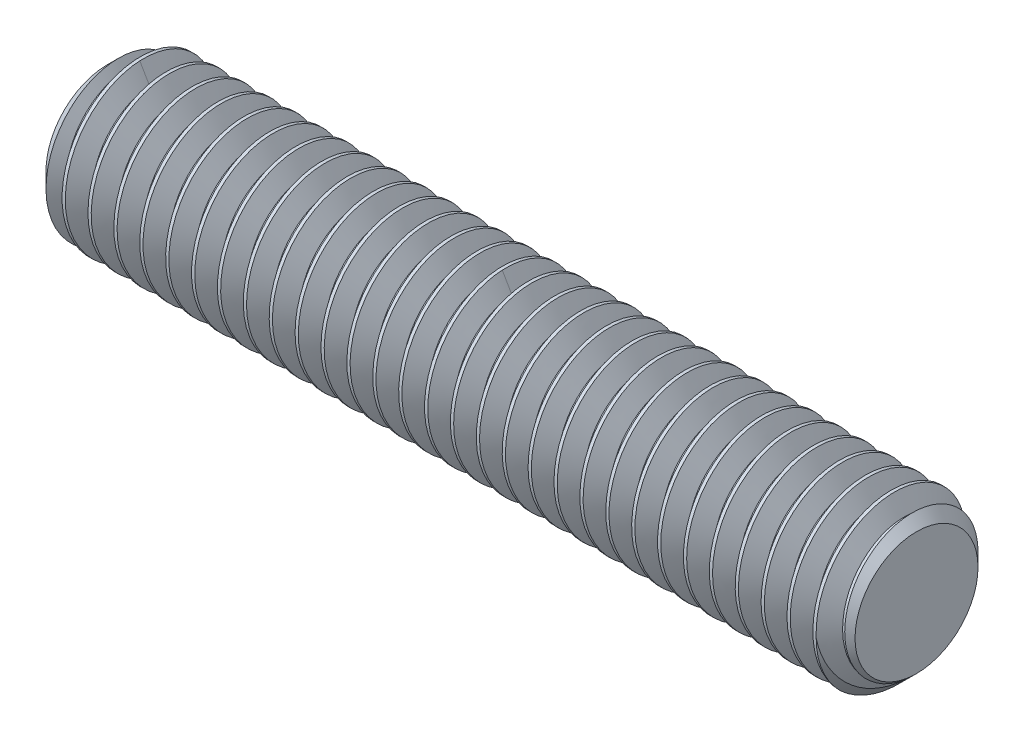
SolidWorks part; units mm, degrees
ref_plane "Front Plane" through (0, 0, 0) normal (0, 0, 1) x (1, 0, 0)
ref_plane "Top Plane" through (0, 0, 0) normal (0, 1, 0) x (1, 0, 0)
ref_plane "Right Plane" through (0, 0, 0) normal (1, 0, 0) x (0, 0, -1)
sketch "Sketch1" plane through (0, 0, 0) normal (0, 0, 1) x (1, 0, 0)
  line L0 (-12.5, 0) -> (12.5, 0) construction
  line L1 (12.5, 2.5) -> (12.5, -2.5) construction
  line L2 (-12.5, 2.5) -> (-12.5, -2.5) construction
  line L3 (12.5, 2.5) -> (0.5, 2.5) construction
  line L4 (-12.5, 2.5) -> (-11.7, 2.5) construction
  point P6 (9.7, -2.5)
  point P9 (-2.5, 0)
  point P10 (2.5, 0)
  dimension "Thread Diameter" = 5
  dimension "Length" = 25
  dimension "D1" = 2.8
  dimension "Segment Length" = 12
  dimension "D2" = 10
  dimension "D3" = 10
  dimension "Thread Pitch" = 0.8
sketch "Sketch2" plane through (0, 0, 0) normal (1, 0, 0) x (0, 0, -1)
  circle A0 centre (0, 0) radius 2.5
extrude "Boss-Extrude1" add sketch "Sketch2" against normal up to vertex (12.5 mm away) and the other way up to vertex (12.5 mm away) up to point (-12.5, 0, 0) other way up to point (12.5, 0, 0)
chamfer "Chamfer1" distance 0.6 angle 45 2 edges at (-12.5, 0, -2.5) (12.5, 0, -2.5)
sketch "Drawing1" plane through (0, 0, 0) normal (1, 0, 0) x (0, 0, -1)
  circle A0 centre (0, 0) radius 2.5
sketch "Sketch3" plane through (12.5, 0, 0) normal (1, 0, 0) x (0, 0, -1)
  circle A1 centre (0, 0) radius 2.5
  circle A2 centre (0, 0) radius 2.5
  dimension "D1" = 0
curve "Helix/Spiral1" pitch 0.8 height 12.8 turns 16 parameters "Pitch"=0.8
sketch "Sketch4" plane through (0, 0, 0) normal (0, 0, 1) x (1, 0, 0)
  line L0 (12.45, 2.5866) -> (12.85, 1.8938) construction
  line L1 (12.85, 1.8938) -> (13.25, 2.5866) construction
  line L2 (13.25, 2.5866) -> (12.45, 2.5866) construction
  line L3 (12.85, 2.5866) -> (12.85, 2.5) construction
  line L4 (12.85, 1.8938) -> (12.85, 1.9804) construction
  line L5 (12.8, 1.9804) -> (12.9, 1.9804) construction
  line L6 (12.5, 2.5) -> (13.2, 2.5) construction
  line L7 (12.8, 1.9804) -> (12.475, 2.5433)
  line L8 (12.8, 1.9804) -> (12.9, 1.9804)
  line L9 (12.475, 2.5433) -> (13.225, 2.5433)
  line L10 (13.225, 2.5433) -> (12.9, 1.9804)
  point P13 (12.85, 2.5433)
  dimension "D2" = 0.1
sweep "Cut-Sweep3" cut profiles "Sketch4" path "Helix/Spiral1"
pattern_linear "LPattern1" count 3 spacing 11.2 along (1, 0, 0) of "Cut-Sweep3"
equation "\"D3@Helix/Spiral1\"=\"Pitch@Helix/Spiral1\"+\"Segment Length@Sketch1\""
equation "\"D1@Chamfer1\" = \"Pitch@Helix/Spiral1\"*.75"
equation "\"D1@Sketch4\" = \"Pitch@Helix/Spiral1\""
equation "\"D2@Sketch4\" = \"D1@Sketch4\"/8"
equation "\"D1@Sketch1\" = \"Pitch@Helix/Spiral1\"*3.50"
equation "\"Segment Length@Sketch1\"=\"Pitch@Helix/Spiral1\"*15"
equation "\"D1@LPattern1\"=(\"Length@Sketch1\"/(\"Segment Length@Sketch1\"-\"Pitch@Helix/Spiral1\"))+1"
equation "\"D3@LPattern1\"=\"Segment Length@Sketch1\"-\"Pitch@Helix/Spiral1\""
equation "\"D2@Sketch1\"=\"Thread Diameter@Sketch1\"*2"
equation "\"D3@Sketch1\"=\"Thread Diameter@Sketch1\"*2"
equation "\"Pitch@Helix/Spiral1\"=\"Thread Pitch@Sketch1\""
